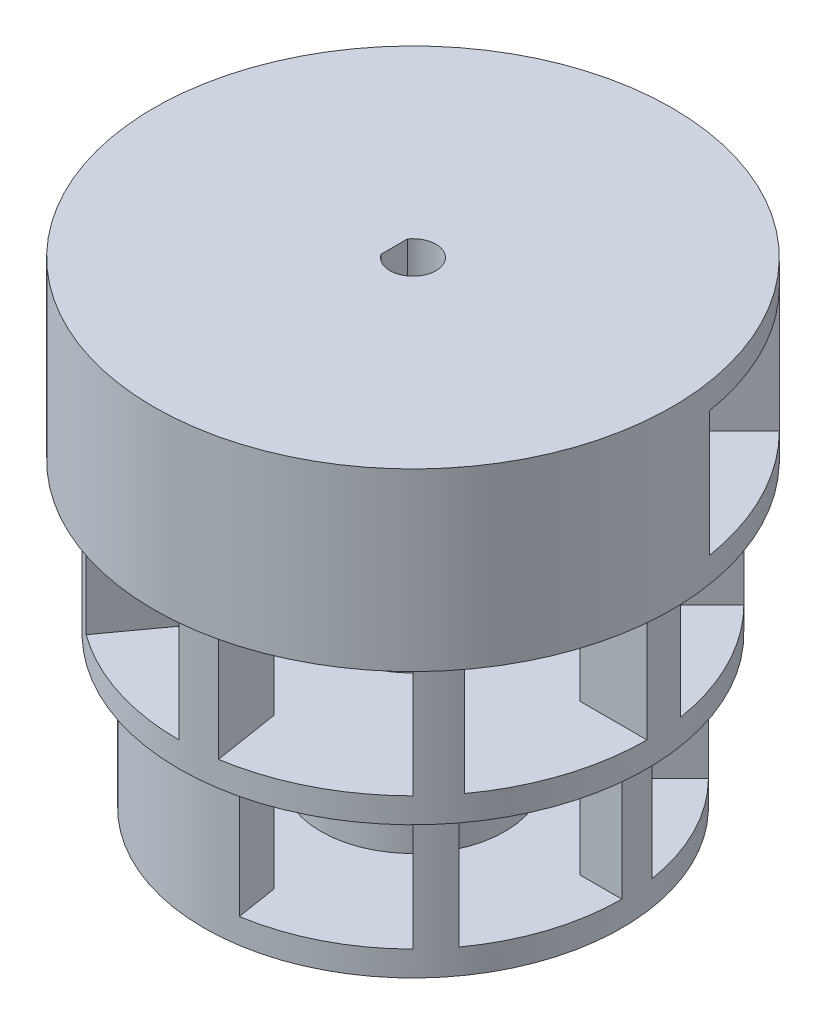
SolidWorks part; units mm, degrees
ref_plane "Front Plane" through (0, 0, 0) normal (0, 0, 1) x (1, 0, 0)
ref_plane "Top Plane" through (0, 0, 0) normal (0, 1, 0) x (1, 0, 0)
ref_plane "Right Plane" through (0, 0, 0) normal (1, 0, 0) x (0, 0, -1)
sketch "Sketch1" plane through (0, 0, 0) normal (0, 1, 0) x (1, 0, 0)
  circle A0 centre (0, 0) radius 25
  circle A1 centre (0, 0) radius 8
  dimension "D1" = 50
  dimension "D2" = 16
extrude "Boss-Extrude1" add sketch "Sketch1" along normal blind 3
sketch "Sketch2" plane through (0, 3, 0) normal (0, 1, 0) x (1, 0, 0)
  circle A0 centre (0, 0) radius 11
extrude "Boss-Extrude2" add sketch "Sketch2" along normal blind 3
sketch "Sketch3" plane through (0, 3, 0) normal (0, 1, 0) x (1, 0, 0)
  line L0 (-14.1421, -14.1421) -> (-16.2635, -16.2635)
  line L1 (-11.7557, -16.1803) -> (-13.5191, -18.6074)
  line L2 (0, -20) -> (0, -23)
  line L3 (3.1287, -19.7538) -> (3.9109, -24.6922)
  line L4 (-20, 0) -> (-23, 0)
  line L5 (-19.7538, -3.1287) -> (-22.7168, -3.598)
  line L6 (-14.1421, 14.1421) -> (-16.2635, 16.2635)
  line L7 (-16.1803, 11.7557) -> (-18.6074, 13.5191)
  line L8 (0, 20) -> (0, 25)
  line L9 (-3.1287, 19.7538) -> (-3.598, 22.7168)
  line L10 (14.1421, 14.1421) -> (17.6777, 17.6777)
  line L11 (11.7557, 16.1803) -> (14.6946, 20.2254)
  line L12 (20, 0) -> (25, 0)
  line L13 (19.7538, 3.1287) -> (24.6922, 3.9109)
  line L14 (14.1421, -14.1421) -> (17.6777, -17.6777)
  line L15 (16.1803, -11.7557) -> (20.2254, -14.6946)
  circle A0 centre (0, 0) radius 8
  circle A1 centre (0, 0) radius 25 construction
  circle A2 centre (0, 0) radius 10
  arc A3 (0, -20) -> (3.1287, -19.7538) centre (0, 0) ccw
  arc A4 (-13.5191, -18.6074) -> (0, -23) centre (0, 0) ccw
  arc A5 (-14.1421, -14.1421) -> (-11.7557, -16.1803) centre (0, 0) ccw
  arc A6 (-22.7168, -3.598) -> (-16.2635, -16.2635) centre (0, 0) ccw
  arc A7 (-20, 0) -> (-19.7538, -3.1287) centre (0, 0) ccw
  arc A9 (-14.1421, 14.1421) -> (-16.1803, 11.7557) centre (0, 0) ccw
  arc A10 (-18.6074, 13.5191) -> (-23, 0) centre (0, 0) ccw
  arc A11 (0, 20) -> (-3.1287, 19.7538) centre (0, 0) ccw
  arc A12 (17.6777, 17.6777) -> (14.6946, 20.2254) centre (0, 0) ccw
  arc A13 (14.1421, 14.1421) -> (11.7557, 16.1803) centre (0, 0) ccw
  arc A14 (25, 0) -> (24.6922, 3.9109) centre (0, 0) ccw
  arc A15 (20, 0) -> (19.7538, 3.1287) centre (0, 0) ccw
  arc A16 (17.6777, -17.6777) -> (20.2254, -14.6946) centre (0, 0) ccw
  arc A17 (14.1421, -14.1421) -> (16.1803, -11.7557) centre (0, 0) ccw
  arc A18 (-3.598, 22.7168) -> (-16.2635, 16.2635) centre (0, 0) ccw
  arc A19 (0, 25) -> (14.6946, 20.2254) centre (0, 0) ccw
  point P40 (0, 0)
  circle M1 centre (0, 0) radius 25
  dimension "D1" = 9
  dimension "D2" = 20
  dimension "D3" = 8
extrude "Boss-Extrude3" add sketch "Sketch3" along normal blind 15 contours A18 L9 A11 L8 L3 A3 L2 A4 L1 A5 L0 A6 L5 A7 L4 A10 L7 A9 L6 M1 | A2 A0 | A17 L14 L15 M1 | A15 L12 L13 M1 | A13 L10 L11 M1 region at (-13.3641, 3, 15.6473) region at (17.1619, 3, 14.6576) region at (14.6576, 3, -17.1619) region at (22.4998, 3, -1.7708) region at (-9.7172, 3, 0)
sketch "Sketch4" plane through (0, 18, 0) normal (0, 1, 0) x (1, 0, 0)
  circle A0 centre (0, 0) radius 8
  circle A1 centre (0, 0) radius 28
extrude "Boss-Extrude4" add sketch "Sketch4" along normal blind 3
sketch "Sketch6" plane through (0, 21, 0) normal (0, 1, 0) x (1, 0, 0)
  line L0 (-11.7557, -16.1803) -> (-16.458, -22.6525)
  line L1 (3.1287, -19.7538) -> (4.3802, -27.6553)
  line L2 (0, -20) -> (0, -28)
  line L3 (-14.1421, -14.1421) -> (-19.799, -19.799)
  line L4 (-19.7538, -3.1287) -> (-27.6553, -4.3802)
  line L5 (-20, 0) -> (-28, 0)
  line L6 (-16.1803, 11.7557) -> (-22.6525, 16.458)
  line L7 (-14.1421, 14.1421) -> (-19.799, 19.799)
  line L8 (-3.1287, 19.7538) -> (-4.3802, 27.6553)
  line L9 (0, 20) -> (0, 28)
  line L10 (11.7557, 16.1803) -> (16.458, 22.6525)
  line L11 (14.1421, 14.1421) -> (19.799, 19.799)
  line L12 (19.7538, 3.1287) -> (27.6553, 4.3802)
  line L13 (20, 0) -> (28, 0)
  line L14 (16.1803, -11.7557) -> (22.6525, -16.458)
  line L15 (14.1421, -14.1421) -> (19.799, -19.799)
  arc A0 (0, -20) -> (3.1287, -19.7538) centre (0, 0) ccw
  arc A1 (0, -28) -> (4.3802, -27.6553) centre (0, 0) ccw
  circle A2 centre (0, 0) radius 8
  circle A3 centre (0, 0) radius 10
  arc A4 (-14.1421, -14.1421) -> (-11.7557, -16.1803) centre (0, 0) ccw
  arc A5 (-19.799, -19.799) -> (-16.458, -22.6525) centre (0, 0) ccw
  arc A6 (-20, 0) -> (-19.7538, -3.1287) centre (0, 0) ccw
  arc A7 (-28, 0) -> (-27.6553, -4.3802) centre (0, 0) ccw
  arc A8 (-14.1421, 14.1421) -> (-16.1803, 11.7557) centre (0, 0) ccw
  arc A9 (-19.799, 19.799) -> (-22.6525, 16.458) centre (0, 0) ccw
  arc A10 (0, 20) -> (-3.1287, 19.7538) centre (0, 0) ccw
  arc A11 (0, 28) -> (-4.3802, 27.6553) centre (0, 0) ccw
  arc A12 (14.1421, 14.1421) -> (11.7557, 16.1803) centre (0, 0) ccw
  arc A13 (19.799, 19.799) -> (16.458, 22.6525) centre (0, 0) ccw
  arc A14 (20, 0) -> (19.7538, 3.1287) centre (0, 0) ccw
  arc A15 (28, 0) -> (27.6553, 4.3802) centre (0, 0) ccw
  arc A16 (14.1421, -14.1421) -> (16.1803, -11.7557) centre (0, 0) ccw
  arc A17 (19.799, -19.799) -> (22.6525, -16.458) centre (0, 0) ccw
  point P38 (0, 0)
  dimension "D1" = 8
extrude "Boss-Extrude5" add sketch "Sketch6" along normal blind 15
sketch "Sketch7" plane through (0, 36, 0) normal (0, 1, 0) x (1, 0, 0)
  circle A0 centre (0, 0) radius 31
  circle A1 centre (0, 0) radius 8
extrude "Boss-Extrude6" add sketch "Sketch7" along normal blind 3
sketch "Sketch9" plane through (0, 39, 0) normal (0, 1, 0) x (1, 0, 0)
  line L0 (0, -20) -> (0, -28)
  line L1 (3.1287, -19.7538) -> (4.3802, -27.6553)
  line L2 (-14.1421, -14.1421) -> (-19.799, -19.799)
  line L3 (-11.7557, -16.1803) -> (-16.458, -22.6525)
  line L4 (-20, 0) -> (-31, 0)
  line L5 (-19.7538, -3.1287) -> (-27.6553, -4.3802)
  line L6 (-14.1421, 14.1421) -> (-21.9203, 21.9203)
  line L7 (-16.1803, 11.7557) -> (-25.0795, 18.2213)
  line L8 (0, 20) -> (0, 31)
  line L9 (-3.1287, 19.7538) -> (-4.8495, 30.6183)
  line L10 (14.1421, 14.1421) -> (21.9203, 21.9203)
  line L11 (11.7557, 16.1803) -> (18.2213, 25.0795)
  line L12 (20, 0) -> (28, 0)
  line L13 (19.7538, 3.1287) -> (30.6183, 4.8495)
  line L14 (14.1421, -14.1421) -> (19.799, -19.799)
  line L15 (16.1803, -11.7557) -> (22.6525, -16.458)
  arc A1 (0, -20) -> (3.1287, -19.7538) centre (0, 0) ccw
  arc A2 (22.6525, -16.458) -> (28, 0) centre (0, 0) ccw
  circle A3 centre (0, 0) radius 8
  circle A4 centre (0, 0) radius 10
  arc A5 (-14.1421, -14.1421) -> (-11.7557, -16.1803) centre (0, 0) ccw
  arc A6 (4.3802, -27.6553) -> (19.799, -19.799) centre (0, 0) ccw
  arc A7 (-20, 0) -> (-19.7538, -3.1287) centre (0, 0) ccw
  arc A8 (-16.458, -22.6525) -> (0, -28) centre (0, 0) ccw
  arc A9 (-14.1421, 14.1421) -> (-16.1803, 11.7557) centre (0, 0) ccw
  arc A10 (-21.9203, 21.9203) -> (-25.0795, 18.2213) centre (0, 0) ccw
  arc A11 (0, 20) -> (-3.1287, 19.7538) centre (0, 0) ccw
  arc A12 (0, 31) -> (-4.8495, 30.6183) centre (0, 0) ccw
  arc A13 (14.1421, 14.1421) -> (11.7557, 16.1803) centre (0, 0) ccw
  arc A14 (21.9203, 21.9203) -> (18.2213, 25.0795) centre (0, 0) ccw
  arc A15 (20, 0) -> (19.7538, 3.1287) centre (0, 0) ccw
  arc A17 (14.1421, -14.1421) -> (16.1803, -11.7557) centre (0, 0) ccw
  arc A19 (-27.6553, -4.3802) -> (-19.799, -19.799) centre (0, 0) ccw
  arc A20 (-31, 0) -> (30.5735, 5.1248) centre (0, 0) ccw
  point P43 (0, 0)
  circle M1 centre (0, 0) radius 31
  circle M2 centre (0, 0) radius 8
  dimension "D1" = 8
extrude "Boss-Extrude7" add sketch "Sketch9" along normal blind 15 contours A19 L5 A7 L4 L13 A15 L12 A2 L15 A17 L14 A6 L1 A1 L0 A8 L3 A5 L2 M1 | A4 M2 | A13 L10 L11 M1 | A11 L8 L9 M1 | A9 L6 L7 M1 region at (1.6254, 39, 20.6523) region at (-19.6708, 39, -16.8004) region at (-2.0296, 39, -25.7891) region at (16.8004, 39, -19.6708) region at (-9.7172, 39, 0)
sketch "Sketch10" plane through (0, 54, 0) normal (0, 1, 0) x (1, 0, 0)
  circle A0 centre (0, 0) radius 31
  circle A1 centre (0, 0) radius 8
extrude "Boss-Extrude8" add sketch "Sketch10" along normal blind 3
sketch "Sketch11" plane through (0, 0, 0) normal (0, 0, 1) x (1, 0, 0)
  line L0 (8, 57) -> (2.75, 57)
  line L1 (2.75, 57) -> (2.75, 47)
  line L2 (2.75, 47) -> (0, 47)
  line L3 (0, 47) -> (0, 44.5)
  line L4 (8, 48.8208) -> (7.3757, 48.8208)
  line L6 (8, 57) -> (8, 48.8208)
  line L7 (0, 42) -> (0, 63.5698) construction
  arc A0 (0, 44.5) -> (7.3757, 48.8208) centre (0, 52.9557) ccw
  dimension "D1" = 2.5
  dimension "D2" = 10
  dimension "D3" = 5.5
revolve "Revolve1" add sketch "Sketch11" angle 360 about L7
sketch "Sketch12" plane through (0, 57, 0) normal (0, 1, 0) x (1, 0, 0)
  line L0 (0, 2.9812) -> (0, -2.9417) construction
  line L1 (-2.25, -5.1436) -> (-7.009, -5.1436)
  line L2 (-2.25, -5.1436) -> (-2.25, 7.2367)
  line L3 (-2.25, 7.2367) -> (-7.009, 7.2367)
  line L4 (-7.009, -5.1436) -> (-7.009, 7.2367)
  dimension "D1" = 2.25
extrude "Boss-Extrude9" add sketch "Sketch12" against normal up to next
ref_plane "Plane3" through (16.948, 0, -8.6354) normal (0.891, 0, -0.454) x (-0.454, 0, -0.891)
sketch "Sketch20" plane through (16.948, 0, -8.6354) normal (0.891, 0, -0.454) x (-0.454, 0, -0.891)
  line L0 (0, 8) -> (0, 16) construction
  line L1 (-1.75, 8) -> (-1.75, 16)
  line L2 (1.75, 8) -> (1.75, 16)
  line L3 (-28, 18) -> (28, 18) construction
  arc A0 (-1.75, 8) -> (1.75, 8) centre (0, 8) ccw
  arc A1 (1.75, 16) -> (-1.75, 16) centre (0, 16) ccw
  point P2 (0, 12)
  dimension "D1" = 3.5
  dimension "D2" = 8
  dimension "D3" = 6
extrude "Cut-Extrude7" cut sketch "Sketch20" against normal up to next
pattern_circular "CirPattern3" count 8 every 45 about axis through (0, 3, 0) along (0, -1, 0) of "Cut-Extrude7"
ref_plane "Plane6" through (8.229, 0, -25.3262) normal (0.309, 0, -0.9511) x (-0.9511, 0, -0.309)
sketch "Sketch18" plane through (8.229, 0, -25.3262) normal (0.309, 0, -0.9511) x (-0.9511, 0, -0.309)
  line L0 (0, 24.2083) -> (0, 32.2083) construction
  line L1 (-2, 24.2083) -> (-2, 32.2083)
  line L2 (2, 24.2083) -> (2, 32.2083)
  arc A1 (-2, 24.2083) -> (2, 24.2083) centre (0, 24.2083) ccw
  arc A2 (2, 32.2083) -> (-2, 32.2083) centre (0, 32.2083) ccw
  point P5 (0, 28.2083)
  dimension "D2" = 4
  dimension "D3" = 8
extrude "Cut-Extrude5" cut sketch "Sketch18" against normal up to next
pattern_circular "CirPattern1" count 8 every 45 about axis through (0, 57, 0) along (0, -1, 0) of "Cut-Extrude5"
ref_plane "Plane7" through (16.948, 0, -8.6354) normal (0.891, 0, -0.454) x (-0.454, 0, -0.891)
sketch "Sketch19" plane through (16.948, 0, -8.6354) normal (0.891, 0, -0.454) x (-0.454, 0, -0.891)
  line L1 (0, 51) -> (0, 42) construction
  line L2 (2.25, 51) -> (2.25, 42)
  line L3 (-2.25, 51) -> (-2.25, 42)
  line L4 (-6.1803, 46.5) -> (6.1803, 46.5) construction
  line L5 (-6.1803, 54) -> (-6.1803, 39) construction
  line L6 (6.1803, 54) -> (6.1803, 39) construction
  arc A0 (2.25, 51) -> (-2.25, 51) centre (0, 51) ccw
  arc A1 (-2.25, 42) -> (2.25, 42) centre (0, 42) ccw
  point P2 (0, 46.5)
  dimension "D2" = 9
  dimension "D1" = 4.5
extrude "Cut-Extrude6" cut sketch "Sketch19" against normal blind 12.5
pattern_circular "CirPattern2" count 8 every 45 about axis through (0, 39, 0) along (0, -1, 0) of "Cut-Extrude6"
